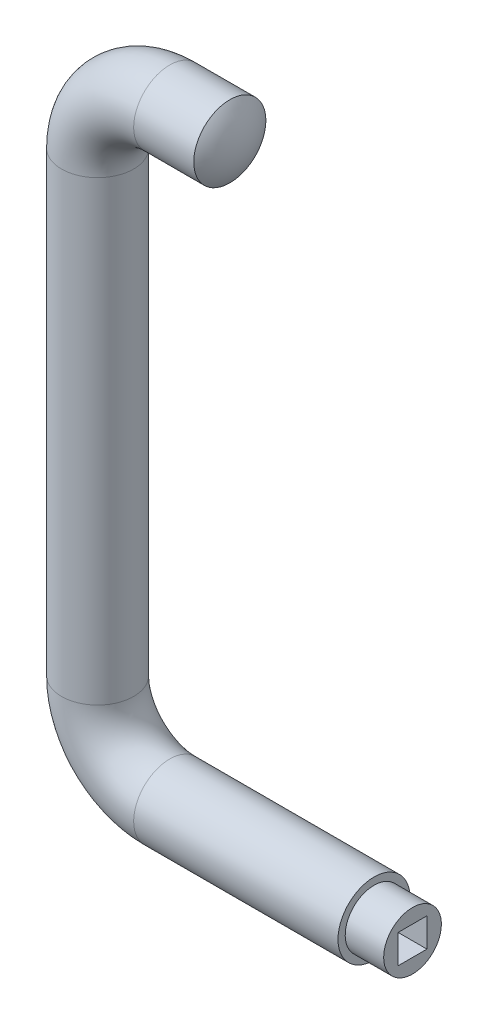
SolidWorks part; units mm, degrees
ref_plane "Front Plane" through (0, 0, 0) normal (0, 0, 1) x (1, 0, 0)
ref_plane "Top Plane" through (0, 0, 0) normal (0, 1, 0) x (1, 0, 0)
ref_plane "Right Plane" through (0, 0, 0) normal (1, 0, 0) x (0, 0, -1)
sketch "Sketch2" plane through (0, 0, 0) normal (0, 0, 1) x (1, 0, 0)
  line L0 (0, 0) -> (-34.5, 0)
  line L1 (-49.5, 15) -> (-49.5, 110)
  line L2 (-34.5, 125) -> (-22, 125)
  arc A0 (-34.5, 0) -> (-49.5, 15) centre (-34.5, 15) cw
  arc A1 (-49.5, 110) -> (-34.5, 125) centre (-34.5, 110) cw
  point P9 (-43.5853, 2.1205)
  point P10 (-49.5, 125)
  dimension "D1" = 15
  dimension "D2" = 49.5
  dimension "D5" = 15
  dimension "D3" = 125
  dimension "D4" = 27.5
sweep "Sweep-Thin1" add path "Sketch2" circular profile diameter 15 parameters "D1"=1.5, "D3"=15
sketch "Sketch27" plane through (0, 0, 0) normal (0, 0, 1) x (1, 0, 0)
  line L0 (-22, 132.5) -> (-22, 125)
  line L1 (-22, 117.5) -> (-22, 132.5) construction
  line L2 (-22, 125) -> (-19.5, 125)
  arc A0 (-22, 132.5) -> (-19.5, 125) centre (-32, 125) cw
  dimension "D1" = 12.5
  dimension "D2" = 2.5
revolve "Revolve1" add sketch "Sketch27" angle 360 about L2
sketch "Sketch29" plane through (0, 0, 0) normal (1, 0, 0) x (0, 0, -1)
  circle A1 centre (0, 0) radius 7.5
  circle A2 centre (0, 0) radius 7.5
  dimension "D1" = 0
extrude "Boss-Extrude1" add sketch "Sketch29" along normal blind 8
sketch "Sketch30" plane through (8, 0, 0) normal (1, 0, 0) x (0, 0, -1)
  circle A0 centre (0, 0) radius 6
  dimension "D1" = 12
extrude "Boss-Extrude2" add sketch "Sketch30" along normal blind 8
sketch "Sketch31" plane through (16, 0, 0) normal (1, 0, 0) x (0, 0, -1)
  line L1 (3, -3) -> (-3, -3)
  line L2 (3, -3) -> (3, 3)
  line L3 (3, 3) -> (-3, 3)
  line L4 (-3, -3) -> (-3, 3)
  line L5 (3, -3) -> (-3, 3) construction
  line L6 (3, 3) -> (-3, -3) construction
  point P0 (0, 0)
  dimension "D1" = 6
  dimension "D2" = 6
extrude "Cut-Extrude2" cut sketch "Sketch31" against normal blind 16
